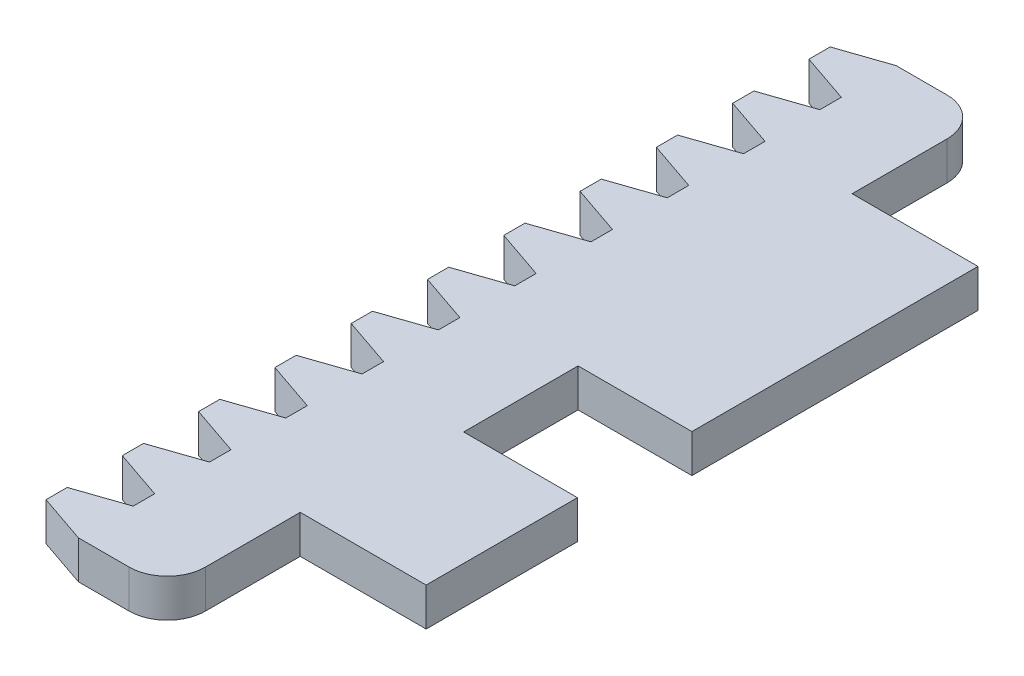
SolidWorks part; units mm, degrees
ref_plane "Front Plane" through (0, 0, 0) normal (0, 0, 1) x (1, 0, 0)
ref_plane "Top Plane" through (0, 0, 0) normal (0, 1, 0) x (1, 0, 0)
ref_plane "Right Plane" through (0, 0, 0) normal (1, 0, 0) x (0, 0, -1)
sketch "Sketch1" plane through (0, 0, 0) normal (0, 1, 0) x (1, 0, 0)
  line L4 (37.95, 21.7) -> (28.05, 21.7) construction
  line L5 (28.05, 29.157) -> (28.05, 21.7) construction
  line L6 (21.0585, 32.157) -> (25.05, 32.157) construction
  line L7 (21.0585, 32.157) -> (17.1887, 30.8335) construction
  line L8 (17.1887, 30.8335) -> (17.1887, 29.1665) construction
  line L13 (17.1887, 29.1665) -> (21.0585, 27.843) construction
  line L14 (21.0585, 26.157) -> (21.0585, 27.843) construction
  line L15 (21.0585, 26.157) -> (17.1887, 24.8335) construction
  line L16 (17.1887, 24.8335) -> (17.1887, 23.1665) construction
  line L17 (17.1887, 23.1665) -> (21.0585, 21.843) construction
  line L18 (21.0585, 20.157) -> (21.0585, 21.843) construction
  line L19 (21.0585, 20.157) -> (17.1887, 18.8335) construction
  line L20 (17.1887, 18.8335) -> (17.1887, 17.1665) construction
  line L21 (17.1887, 17.1665) -> (21.0585, 15.843) construction
  line L22 (21.0585, 14.157) -> (21.0585, 15.843) construction
  line L23 (21.0585, 14.157) -> (17.1887, 12.8335) construction
  line L24 (17.1887, 12.8335) -> (17.1887, 11.1665) construction
  line L25 (17.1887, 11.1665) -> (21.0585, 9.843) construction
  line L26 (21.0585, 8.157) -> (21.0585, 9.843) construction
  line L27 (21.0585, 8.157) -> (17.1887, 6.8335) construction
  line L28 (17.1887, 6.8335) -> (17.1887, 5.1665) construction
  line L29 (17.1887, 5.1665) -> (21.0585, 3.843) construction
  line L30 (21.0585, 2.157) -> (21.0585, 3.843) construction
  line L31 (21.0585, 2.157) -> (17.1887, 0.8335) construction
  line L32 (17.1887, 0.8335) -> (17.1887, -0.8335) construction
  line L33 (17.1887, -0.8335) -> (21.0585, -2.157) construction
  line L34 (21.0585, -3.843) -> (21.0585, -2.157) construction
  line L35 (21.0585, -3.843) -> (17.1887, -5.1665) construction
  line L36 (17.1887, -5.1665) -> (17.1887, -6.8335) construction
  line L37 (17.1887, -6.8335) -> (21.0585, -8.157) construction
  line L38 (21.0585, -9.843) -> (21.0585, -8.157) construction
  line L39 (21.0585, -9.843) -> (17.1887, -11.1665) construction
  line L40 (17.1887, -11.1665) -> (17.1887, -12.8335) construction
  line L41 (17.1887, -12.8335) -> (21.0585, -14.157) construction
  line L42 (21.0585, -15.843) -> (21.0585, -14.157) construction
  line L43 (21.0585, -15.843) -> (17.1887, -17.1665) construction
  line L44 (17.1887, -17.1665) -> (17.1887, -18.8335) construction
  line L45 (17.1887, -18.8335) -> (21.0585, -20.157) construction
  line L46 (21.0585, -21.843) -> (21.0585, -20.157) construction
  line L47 (21.0585, -21.843) -> (17.1887, -23.1665) construction
  line L48 (17.1887, -23.1665) -> (17.1887, -24.8335) construction
  line L49 (17.1887, -24.8335) -> (21.0585, -26.157) construction
  line L55 (21.0585, -27.843) -> (21.0585, -26.157) construction
  line L56 (21.0585, -27.843) -> (17.1887, -29.1665) construction
  line L57 (17.1887, -29.1665) -> (17.1887, -30.8335) construction
  line L99 (17.1887, -30.8335) -> (21.0585, -32.157) construction
  line L100 (25.05, -32.157) -> (21.0585, -32.157) construction
  line L105 (28.05, -21.7) -> (28.05, -29.157) construction
  line L107 (37.95, -21.7) -> (28.05, -21.7) construction
  line L108 (37.95, -9.8) -> (37.95, -21.7) construction
  line L109 (29, -9.8) -> (37.95, -9.8) construction
  line L110 (29, -0.8) -> (29, -9.8) construction
  line L111 (37.95, -0.8) -> (29, -0.8) construction
  line L112 (37.95, 21.7) -> (37.95, -0.8) construction
  line L113 (37.95, 21.7) -> (28.05, 21.7)
  line L114 (28.05, 29.157) -> (28.05, 21.7)
  line L115 (21.0585, 32.157) -> (25.05, 32.157)
  line L116 (21.0585, 32.157) -> (17.1887, 30.8335)
  line L117 (17.1887, 30.8335) -> (17.1887, 29.1665)
  line L118 (17.1887, 29.1665) -> (21.0585, 27.843)
  line L119 (21.0585, 26.157) -> (21.0585, 27.843)
  line L120 (21.0585, 26.157) -> (17.1887, 24.8335)
  line L121 (17.1887, 24.8335) -> (17.1887, 23.1665)
  line L122 (17.1887, 23.1665) -> (21.0585, 21.843)
  line L123 (21.0585, 20.157) -> (21.0585, 21.843)
  line L124 (21.0585, 20.157) -> (17.1887, 18.8335)
  line L125 (17.1887, 18.8335) -> (17.1887, 17.1665)
  line L126 (17.1887, 17.1665) -> (21.0585, 15.843)
  line L127 (21.0585, 14.157) -> (21.0585, 15.843)
  line L128 (21.0585, 14.157) -> (17.1887, 12.8335)
  line L129 (17.1887, 12.8335) -> (17.1887, 11.1665)
  line L130 (17.1887, 11.1665) -> (21.0585, 9.843)
  line L131 (21.0585, 8.157) -> (21.0585, 9.843)
  line L132 (21.0585, 8.157) -> (17.1887, 6.8335)
  line L133 (17.1887, 6.8335) -> (17.1887, 5.1665)
  line L134 (17.1887, 5.1665) -> (21.0585, 3.843)
  line L135 (21.0585, 2.157) -> (21.0585, 3.843)
  line L136 (21.0585, 2.157) -> (17.1887, 0.8335)
  line L137 (17.1887, 0.8335) -> (17.1887, -0.8335)
  line L138 (17.1887, -0.8335) -> (21.0585, -2.157)
  line L139 (21.0585, -3.843) -> (21.0585, -2.157)
  line L140 (21.0585, -3.843) -> (17.1887, -5.1665)
  line L141 (17.1887, -5.1665) -> (17.1887, -6.8335)
  line L142 (17.1887, -6.8335) -> (21.0585, -8.157)
  line L143 (21.0585, -9.843) -> (21.0585, -8.157)
  line L144 (21.0585, -9.843) -> (17.1887, -11.1665)
  line L145 (17.1887, -11.1665) -> (17.1887, -12.8335)
  line L146 (17.1887, -12.8335) -> (21.0585, -14.157)
  line L147 (21.0585, -15.843) -> (21.0585, -14.157)
  line L148 (21.0585, -15.843) -> (17.1887, -17.1665)
  line L149 (17.1887, -17.1665) -> (17.1887, -18.8335)
  line L150 (17.1887, -18.8335) -> (21.0585, -20.157)
  line L151 (21.0585, -21.843) -> (21.0585, -20.157)
  line L152 (21.0585, -21.843) -> (17.1887, -23.1665)
  line L153 (17.1887, -23.1665) -> (17.1887, -24.8335)
  line L154 (17.1887, -24.8335) -> (21.0585, -26.157)
  line L155 (21.0585, -27.843) -> (21.0585, -26.157)
  line L156 (21.0585, -27.843) -> (17.1887, -29.1665)
  line L157 (17.1887, -29.1665) -> (17.1887, -30.8335)
  line L160 (17.1887, -30.8335) -> (21.0585, -32.157)
  line L161 (25.05, -32.157) -> (21.0585, -32.157)
  line L162 (28.05, -21.7) -> (28.05, -29.157)
  line L163 (37.95, -21.7) -> (28.05, -21.7)
  line L164 (37.95, -9.8) -> (37.95, -21.7)
  line L165 (29, -9.8) -> (37.95, -9.8)
  line L166 (29, -0.8) -> (29, -9.8)
  line L167 (37.95, -0.8) -> (29, -0.8)
  line L168 (37.95, 21.7) -> (37.95, -0.8)
  line L169 (37.95, 28.7) -> (33.35, 28.7) construction
  line L170 (15.05, 32.157) -> (26.5, 32.157) construction
  line L171 (15.05, 32.157) -> (15.05, -32.157) construction
  line L172 (15.05, -32.157) -> (26.5, -32.157) construction
  line L173 (19.65, 32.157) -> (19.65, -32.157) construction
  line L174 (37.95, 28.7) -> (33.35, 28.7) construction
  line L175 (37.95, 28.7) -> (37.95, -28.7) construction
  line L176 (37.95, -28.7) -> (33.35, -28.7) construction
  line L177 (33.35, 28.7) -> (33.35, -28.7) construction
  line L178 (21.0585, 32.157) -> (15.05, 32.157) construction
  line L179 (15.05, -32.157) -> (21.0585, -32.157) construction
  line L180 (15.05, 32.157) -> (15.05, -32.157) construction
  line L181 (19.65, -32.157) -> (19.65, 32.157) construction
  line L182 (37.95, -28.7) -> (33.35, -28.7) construction
  line L183 (33.35, -28.7) -> (33.35, 28.7) construction
  line L184 (37.95, 28.7) -> (37.95, -28.7) construction
  line L185 (37.95, 0) -> (15.05, 0) construction
  line L186 (15.05, 0) -> (37.95, 0) construction
  line L187 (26.5, 32.157) -> (26.5, -32.157) construction
  line L188 (26.5, 32.157) -> (26.5, -32.157) construction
  line L189 (19.65, 21.7) -> (37.95, 21.7) construction
  line L190 (19.65, -21.7) -> (37.95, -21.7) construction
  line L191 (37.95, 21.7) -> (19.65, 21.7) construction
  line L192 (37.95, -3.8) -> (32, -3.8) construction
  line L193 (32, -3.8) -> (32, -6.8) construction
  line L194 (32, -6.8) -> (37.95, -6.8) construction
  line L195 (29, -5.3) -> (37.95, -5.3) construction
  line L196 (34.95, -0.8) -> (34.95, 18.7) construction
  line L197 (34.95, -9.8) -> (34.95, -18.7) construction
  line L198 (34.95, 18.7) -> (19.65, 18.7) construction
  line L199 (19.65, -18.7) -> (34.95, -18.7) construction
  line L200 (34.95, 18.7) -> (34.95, 21.7) construction
  line L201 (34.95, 18.7) -> (37.95, 18.7) construction
  line L202 (34.95, -18.7) -> (37.95, -18.7) construction
  line L203 (34.95, -18.7) -> (34.95, -21.7) construction
  line L204 (37.15, 28.7) -> (37.15, -28.7) construction
  line L205 (34.15, 28.7) -> (34.15, -28.7) construction
  line L206 (18.85, 32.157) -> (18.85, -32.157) construction
  line L207 (15.85, 32.157) -> (15.85, -32.157) construction
  line L208 (37.15, 28.7) -> (37.15, -0.8) construction
  line L209 (34.15, 28.7) -> (34.15, -0.8) construction
  line L210 (18.85, 32.157) -> (18.85, -32.157) construction
  line L211 (15.85, 32.157) -> (15.85, -32.157) construction
  line L212 (37.15, -9.8) -> (37.15, -28.7) construction
  line L213 (34.15, -9.8) -> (34.15, -28.7) construction
  arc A2 (28.05, 29.157) -> (25.05, 32.157) centre (25.05, 29.157) ccw construction
  arc A3 (25.05, -32.157) -> (28.05, -29.157) centre (25.05, -29.157) ccw construction
  arc A4 (28.05, 29.157) -> (25.05, 32.157) centre (25.05, 29.157) ccw
  arc A5 (25.05, -32.157) -> (28.05, -29.157) centre (25.05, -29.157) ccw
sketch "Sketch2" plane through (0, 0, 0) normal (0, 0, 1) x (1, 0, 0)
  line L1 (37.95, -3) -> (15.05, -3)
  line L2 (37.95, -3) -> (37.95, 0)
  line L3 (37.95, 0) -> (15.05, 0)
  line L4 (15.05, -3) -> (15.05, 0)
  line L5 (21, -3) -> (-21, -3) construction
extrude "Boss-Extrude1" add sketch "Sketch1" against normal up to vertex (3 mm away) up to point (15.05, -3, 0)
ref_plane "gear" through (0, 0, 3.8) normal (0, 0, 1) x (1, 0, 0)
ref_plane "front" through (0, 0, 21.7) normal (0, 0, 1) x (1, 0, 0)
ref_plane "back" through (0, 0, -21.7) normal (0, 0, 1) x (1, 0, 0)
ref_plane "top" through (37.15, 0, 0) normal (1, 0, 0) x (0, 0, -1)
ref_plane "bottom" through (15.85, 0, 0) normal (1, 0, 0) x (0, 0, -1)
ref_plane "sym" through (26.5, 0, 0) normal (1, 0, 0) x (0, 0, -1)
